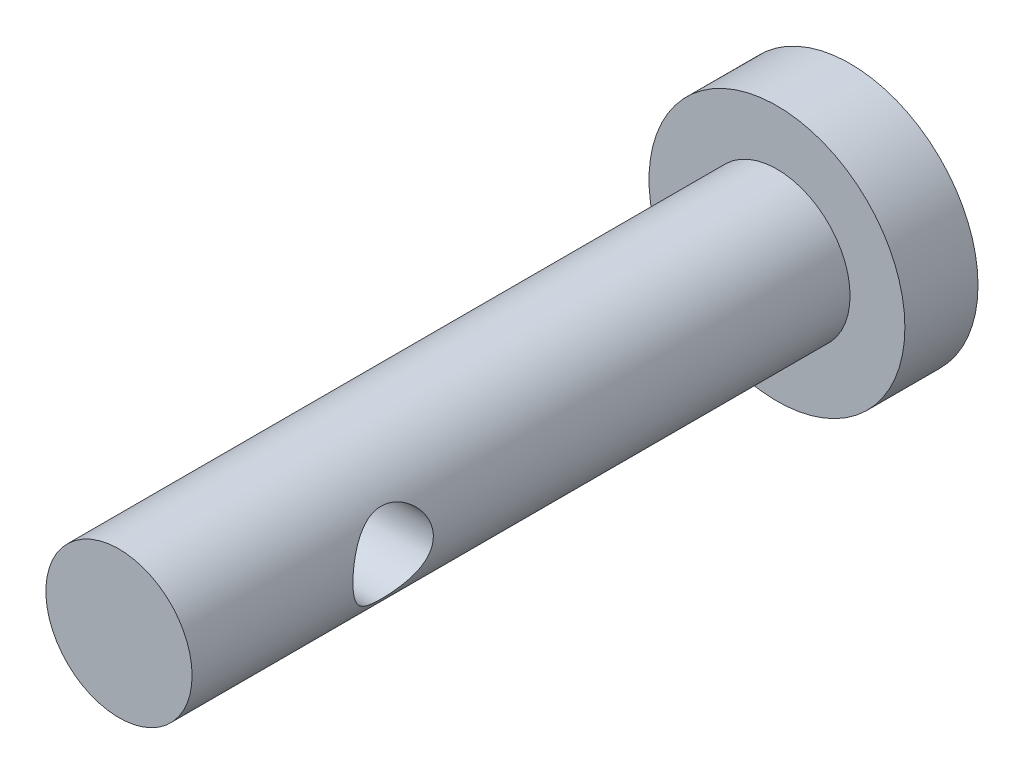
SolidWorks part; units mm, degrees
ref_plane "Płaszczyzna przednia" through (0, 0, 0) normal (0, 0, 1) x (1, 0, 0)
ref_plane "Płaszczyzna górna" through (0, 0, 0) normal (0, 1, 0) x (1, 0, 0)
ref_plane "Płaszczyzna prawa" through (0, 0, 0) normal (1, 0, 0) x (0, 0, -1)
sketch "Szkic1" plane through (0, 0, 0) normal (0, 0, 1) x (1, 0, 0)
  circle A0 centre (0, 0) radius 3.5
extrude "Dodanie-wyciągnięcie1" add sketch "Szkic1" along normal blind 2
sketch "Szkic2" plane through (0, 0, 2) normal (0, 0, 1) x (1, 0, 0)
  circle A0 centre (0, 0) radius 2
extrude "Dodanie-wyciągnięcie2" add sketch "Szkic2" along normal blind 18
ref_plane "Płaszczyzna1" through (-2, 0, 0) normal (-1, 0, 0) x (0, 0, 1)
sketch "Szkic3" plane through (-2, 0, 0) normal (-1, 0, 0) x (0, 0, 1)
  line L0 (2, -2) -> (2, 2) construction
  circle A0 centre (14.5, 0) radius 1.1
  dimension "D1" = 12.5
extrude "Wytnij-wyciągnięcie1" cut sketch "Szkic3" against normal through all
